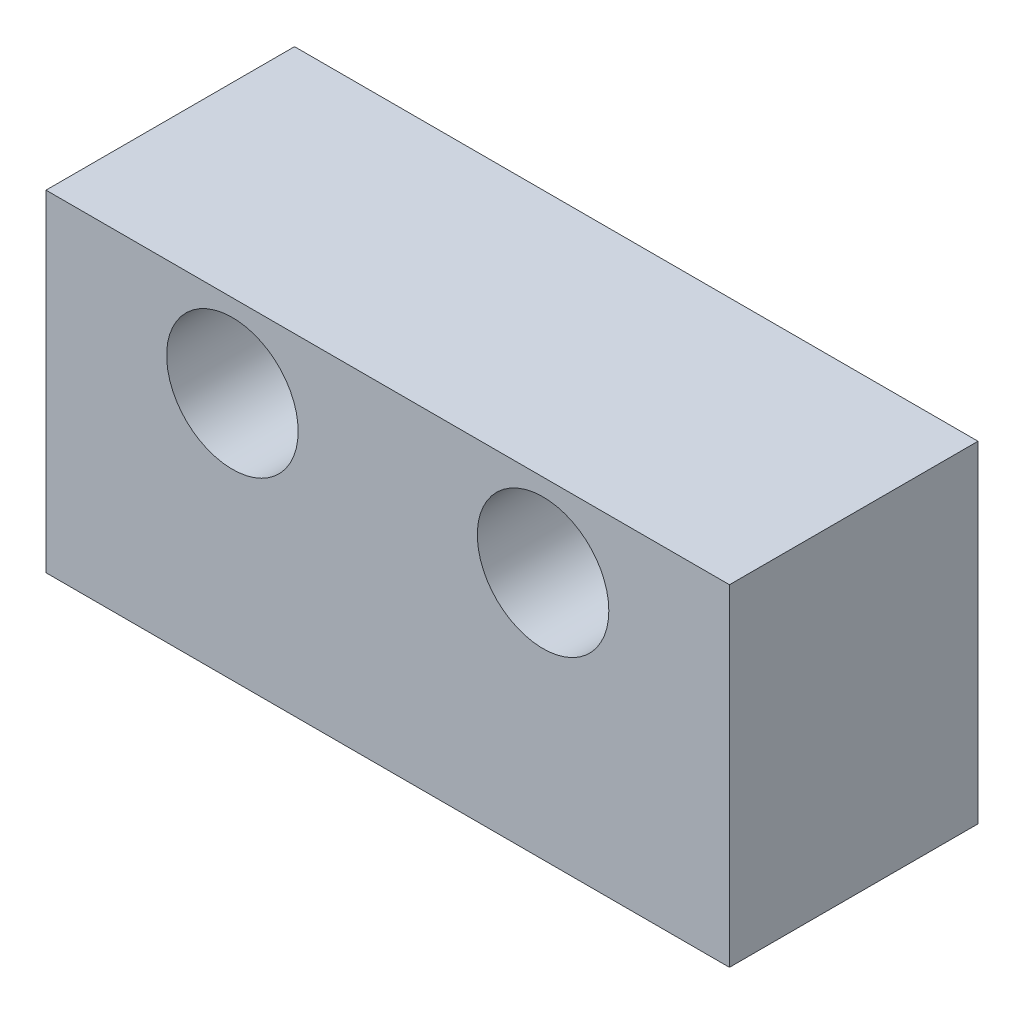
SolidWorks part; units mm, degrees
material "Plain Carbon Steel"
ref_plane "Front Plane" through (0, 0, 0) normal (0, 0, 1) x (1, 0, 0)
ref_plane "Top Plane" through (0, 0, 0) normal (0, 1, 0) x (1, 0, 0)
ref_plane "Right Plane" through (0, 0, 0) normal (1, 0, 0) x (0, 0, -1)
sketch "Sketch1" plane through (0, 0, 0) normal (0, 0, 1) x (1, 0, 0)
  line L0 (-16.5, -12) -> (16.5, -12)
  line L1 (16.5, -12) -> (16.5, 4)
  line L2 (16.5, 4) -> (-16.5, 4)
  line L3 (-16.5, 4) -> (-16.5, -12)
  circle A0 centre (7.5, 0) radius 3.175
  circle A1 centre (-7.5, 0) radius 3.175
  dimension "D2" = 6.35
  dimension "D4" = 6.35
  dimension "D1" = 7.5
  dimension "D3" = 7.5
  dimension "D5" = 33
  dimension "D6" = 16
  dimension "D7" = 16.5
  dimension "D8" = 12
extrude "Boss-Extrude1" add sketch "Sketch1" along normal blind 12
